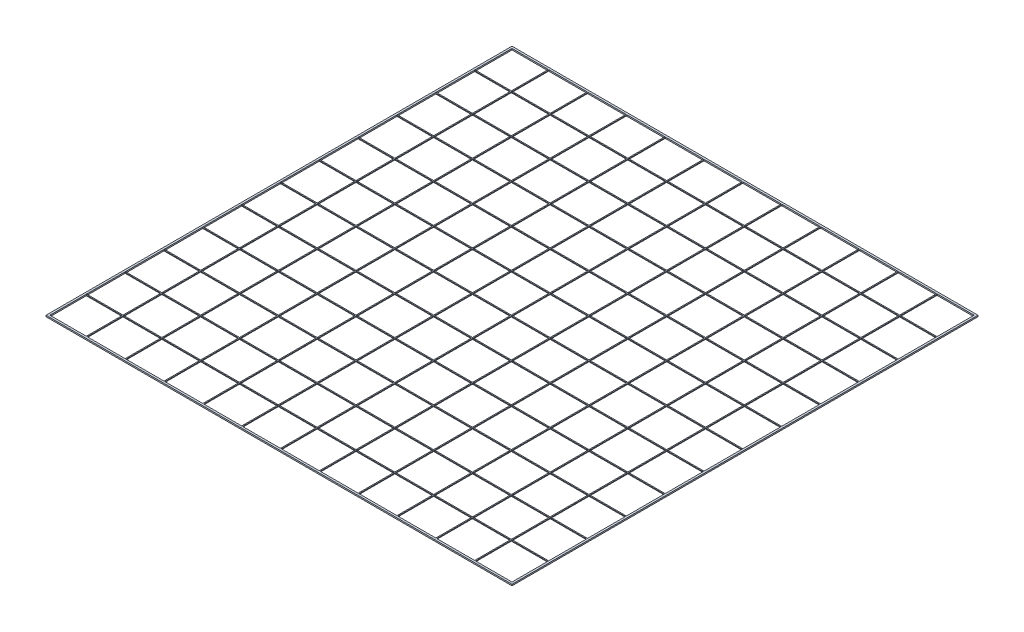
SolidWorks part; units mm, degrees
ref_plane "Front" through (0, 0, 0) normal (0, 0, 1) x (1, 0, 0)
ref_plane "Top" through (0, 0, 0) normal (0, 1, 0) x (1, 0, 0)
ref_plane "Right" through (0, 0, 0) normal (1, 0, 0) x (0, 0, -1)
ref_axis "X" through (-80.9, 0, 0) along (1, 0, 0)
ref_axis "Y" through (0, -50, 0) along (0, 1, 0)
ref_axis "Z" through (0, 0, -80.9) along (0, 0, 1)
sketch "Sketch1" plane through (0, 0, 0) normal (0, 1, 0) x (1, 0, 0)
  line L0 (-94.2, 94.2) -> (94.2, 94.2)
  line L1 (-95, 95) -> (95, 95)
  line L2 (-95, 95) -> (-95, -95)
  line L3 (-95, -95) -> (95, -95)
  line L4 (95, 95) -> (95, -95)
  line L5 (-95, 95) -> (95, -95) construction
  line L6 (-95, -95) -> (95, 95) construction
  line L7 (94.2, 94.2) -> (94.2, -94.2)
  line L8 (-94.2, -94.2) -> (94.2, -94.2)
  line L9 (-94.2, 94.2) -> (-94.2, -94.2)
  point P4 (0, 0)
  point P5 (0, 0)
  dimension "D1" = 190
  dimension "D2" = 0.8
extrude "Boss-Extrude1" add sketch "Sketch1" along normal mid plane 0.56
sketch "Sketch2" plane through (0, 0, 0) normal (0, 1, 0) x (1, 0, 0)
  line L0 (-79.1667, 95) -> (-79.1667, -95) construction
  line L1 (95, 95) -> (-95, 95) construction
  line L2 (-95, -95) -> (95, -95) construction
  line L3 (-95, 95) -> (-95, -95) construction
  line L4 (-79.3667, 95) -> (-79.3667, -95)
  line L5 (-78.9667, 95) -> (-78.9667, -95)
  line L6 (-79.3667, 95) -> (-78.9667, 95)
  line L7 (-79.3667, -95) -> (-78.9667, -95)
  dimension "D1" = 15.8333
  dimension "D2" = 0.2
  dimension "D3" = 0.2
extrude "Boss-Extrude2" add sketch "Sketch2" along normal blind 0.28
pattern_linear "LPattern1" count 11 spacing 15.8333 along (1, 0, 0) of "Boss-Extrude2"
sketch "Sketch3" plane through (0, 0, 0) normal (0, 1, 0) x (1, 0, 0)
  line L0 (-95, 79.1667) -> (95, 79.1667) construction
  line L1 (-95, 95) -> (-95, -95) construction
  line L2 (95, -95) -> (95, 95) construction
  line L3 (95, 95) -> (-95, 95) construction
  line L4 (-95, 78.9667) -> (95, 78.9667)
  line L5 (-95, 79.3667) -> (95, 79.3667)
  line L6 (-95, 78.9667) -> (-95, 79.3667)
  line L7 (95, 78.9667) -> (95, 79.3667)
  dimension "D1" = 15.8333
  dimension "D2" = 0.2
  dimension "D3" = 0.2
extrude "Boss-Extrude3" add sketch "Sketch3" against normal blind 0.28
pattern_linear "LPattern2" count 11 spacing 15.8333 along (0, 0, 1) of "Boss-Extrude3"
